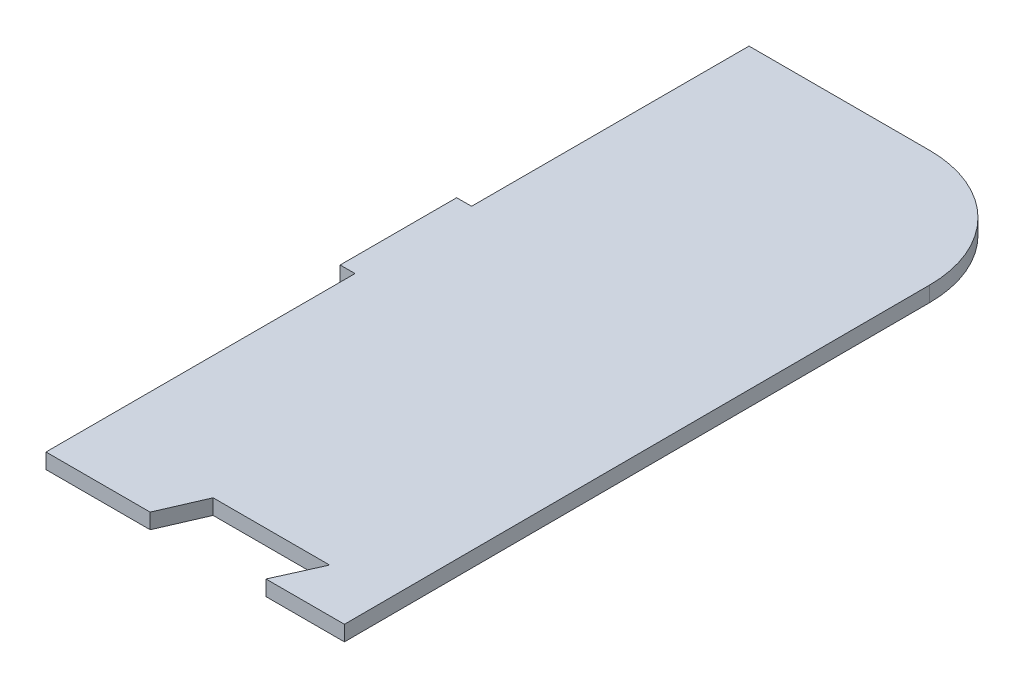
SolidWorks part; units mm, degrees
ref_plane "Front Plane" through (0, 0, 0) normal (0, 0, 1) x (1, 0, 0)
ref_plane "Top Plane" through (0, 0, 0) normal (0, 1, 0) x (1, 0, 0)
ref_plane "Right Plane" through (0, 0, 0) normal (1, 0, 0) x (0, 0, -1)
sketch "Sketch1" plane through (0, 0, 0) normal (0, 0, 1) x (1, 0, 0)
  line L1 (358.1218, 754.38) -> (137.9613, 754.38)
  line L2 (358.1218, 754.38) -> (562.8036, 754.38)
  line L3 (562.8036, 754.38) -> (562.8036, 744.38)
  line L4 (562.8036, 744.38) -> (137.9613, 744.38)
  line L5 (137.9613, 744.38) -> (137.9613, 754.38)
  dimension "D1" = 10
extrude "Boss-Extrude1" add sketch "Sketch1" along normal up to surface (459.74 mm away)
sketch "Sketch3" plane through (0, 744.38, 0) normal (0, -1, 0) x (1, 0, 0)
  line L0 (255.63, 0) -> (255.63, 459.74)
  line L1 (137.9613, 0) -> (562.8036, 0) construction
  line L2 (137.9613, 459.74) -> (562.8036, 459.74) construction
  line L3 (255.63, 459.74) -> (137.9613, 459.74)
  line L4 (137.9613, 459.74) -> (137.9613, 0)
  line L5 (137.9613, 0) -> (255.63, 0)
extrude "Cut-Extrude1" cut sketch "Sketch3" against normal blind 10
sketch "Sketch4" plane through (0, 754.38, 0) normal (0, 1, 0) x (1, 0, 0)
  line L0 (265.3552, -459.74) -> (265.3552, -257.6601)
  line L1 (562.8036, -459.74) -> (255.63, -459.74) construction
  line L2 (562.8036, 0) -> (255.63, 0) construction
  line L3 (265.3552, -459.74) -> (255.63, -459.74)
  line L4 (255.63, -459.74) -> (255.63, -257.6601)
  line L5 (229.0383, -257.6601) -> (265.3552, -257.6601) construction
  line L6 (229.0383, -181.4601) -> (265.3552, -181.4601) construction
  line L7 (265.3552, -459.74) -> (255.63, -459.74)
  line L8 (265.3552, -257.6601) -> (255.63, -257.6601)
  line L9 (265.3552, -181.4601) -> (255.63, -181.4601)
  line L10 (255.63, -181.4601) -> (255.63, 0)
  line L11 (265.3552, -181.4601) -> (265.3552, 0)
  line L12 (333.4642, -459.74) -> (369.7619, -561.8393)
  line L13 (333.4642, -459.74) -> (345.9305, -431.0401)
  line L14 (345.9305, -431.0401) -> (422.1305, -431.0401)
  line L15 (422.1305, -431.0401) -> (409.2168, -459.74)
  line L16 (409.2168, -459.74) -> (460.5019, -459.74)
  line L17 (460.5019, -459.74) -> (459.7218, -76.2)
  line L18 (369.7619, -561.8393) -> (604.2472, -525.6685)
  line L19 (604.2472, -525.6685) -> (681.4814, 161.1092)
  line L20 (681.4814, 161.1092) -> (358.7401, 101.8465)
  line L21 (358.7401, 101.8465) -> (383.5218, 0)
  line L23 (265.3552, 0) -> (255.63, 0)
  line L24 (255.63, -181.4601) -> (255.63, 0)
  arc A1 (459.7218, -76.2) -> (383.5218, 0) centre (383.5218, -76.2) ccw construction
  arc A2 (459.7218, -76.2) -> (383.5218, 0) centre (383.5218, -76.2) ccw
  line M2 (562.8036, 0) -> (255.63, 0)
  line M3 (255.63, 0) -> (255.63, -459.74)
  line M4 (255.63, -459.74) -> (562.8036, -459.74)
  line M5 (562.8036, -459.74) -> (562.8036, 0)
extrude "Cut-Extrude3" cut sketch "Sketch4" against normal blind 63 contours L0 L8 M3 M4 | L9 L11 M2 M3 | L20 L21 L12 L18 L19 M2 M5 M4 | L21 A2 L17 L16 L15 L14 L13 L12 L18 L19 L20 region at (260.4926, 754.38, 358.7) region at (371.3405, 754.38, 467.7635) region at (260.4926, 754.38, 90.73)
